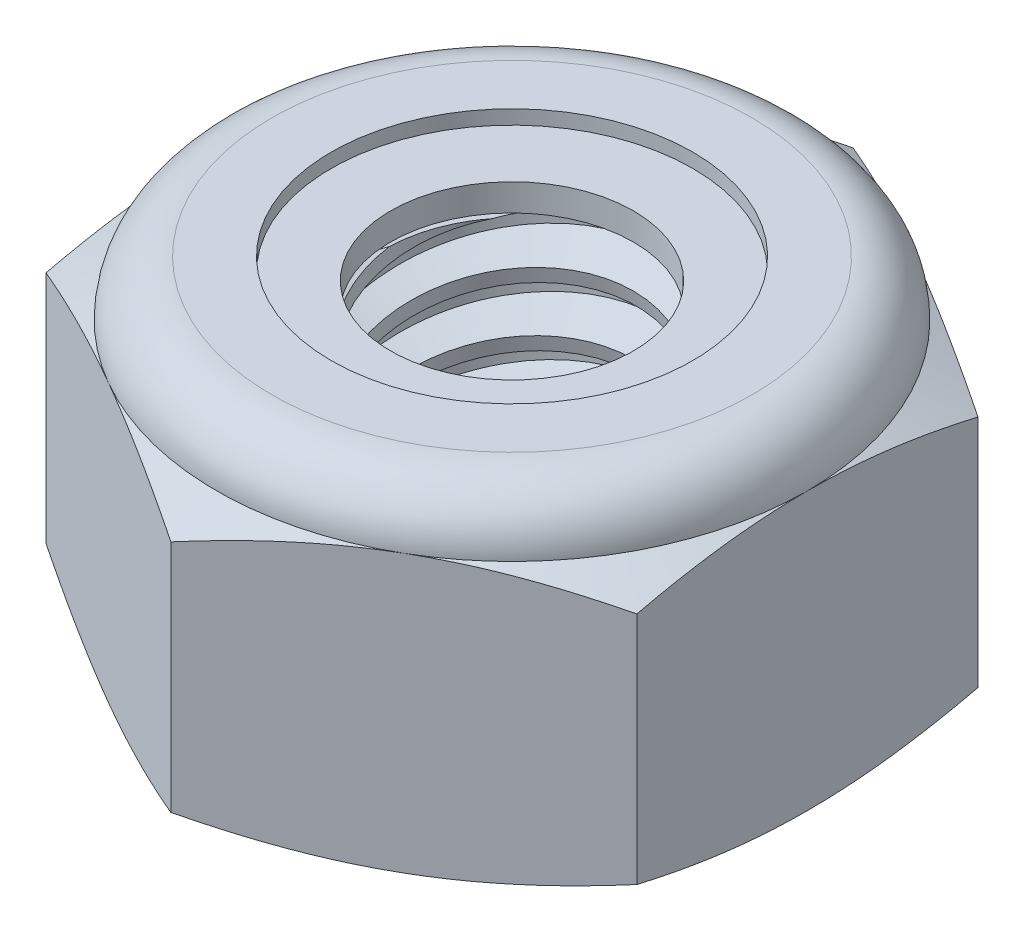
SolidWorks part; units mm, degrees
ref_plane "Front" through (0, 0, 0) normal (0, 0, 1) x (1, 0, 0)
ref_plane "Top" through (0, 0, 0) normal (0, 1, 0) x (1, 0, 0)
ref_plane "Right" through (0, 0, 0) normal (1, 0, 0) x (0, 0, -1)
sketch "Sketch1" plane through (0, 0, 0) normal (0, 1, 0) x (1, 0, 0)
  line L1 (0, 3.6662) -> (-3.175, 1.8331)
  line L2 (-3.175, 1.8331) -> (-3.175, -1.8331)
  line L3 (-3.175, -1.8331) -> (0, -3.6662)
  line L4 (0, -3.6662) -> (3.175, -1.8331)
  line L5 (3.175, -1.8331) -> (3.175, 1.8331)
  line L6 (3.175, 1.8331) -> (0, 3.6662)
  circle A0 centre (0, 0) radius 3.175 construction
  dimension "Hex Flats" = 6.35
extrude "Extrude1" add sketch "Sketch1" along normal blind 3.5719
sketch "Sketch2" plane through (0, 0, 0) normal (1, 0, 0) x (0, 0, -1)
  line L0 (-1.5875, 0) -> (-1.5875, 3.5719) construction
  line L1 (0, 0) -> (1.5875, 0)
  line L2 (0, 0) -> (0, 3.5719)
  line L3 (0, 3.5719) -> (1.5875, 3.5719)
  line L4 (1.5875, 0) -> (1.5875, 3.5719)
  line L5 (-1.8331, 3.5719) -> (1.8331, 3.5719) construction
  line L7 (0, -1.5875) -> (0, 0) construction
  dimension "Thread Dia" = 3.175
revolve "Revolve1" add sketch "Sketch2" angle 360 about L7
sketch "Sketch3" plane through (0, 0, 0) normal (1, 0, 0) x (0, 0, -1)
  line L0 (1.5875, 3.5719) -> (-1.5875, 3.5719) construction
  line L1 (-1.5875, 3.5719) -> (-1.5875, 2.9369) construction
  line L2 (-1.5875, 2.9369) -> (1.5875, 3.5719) construction
  line L3 (1.5875, 3.5719) -> (1.6031, 3.494) construction
  line L4 (1.6031, 3.494) -> (1.712, 2.9492)
  line L5 (1.712, 2.9492) -> (1.3361, 3.0764)
  line L6 (1.3361, 3.0764) -> (1.305, 3.2321)
  line L7 (1.305, 3.2321) -> (1.6031, 3.494)
  line L8 (1.3205, 3.1542) -> (1.6576, 3.2216) construction
  line L9 (1.5875, 3.5719) -> (1.5875, 3.2076) construction
  line L10 (1.5875, 3.2076) -> (-1.5875, 2.5726) construction
  line L11 (-1.5875, 2.5726) -> (-1.5875, 2.9369) construction
  line L12 (-0.1364, 3.5719) -> (0.1364, 2.2084) construction
  line L13 (-1.5875, 0) -> (-1.5875, 3.5719) construction
  line L14 (0, 3.5719) -> (1.5875, 3.5719) construction
  line L15 (1.5875, 0) -> (1.5875, 3.5719) construction
  point P13 (0, 2.8901)
  dimension "D1" = 0.0794
  dimension "D2" = 0.1588
  dimension "Thread Pitch" = 0.635
  dimension "D4" = 60
  dimension "D5" = 0.635
revolve "Cut-Revolve1" cut sketch "Sketch3" angle 360 about L12
pattern_linear "LPattern1" count 6 spacing 0.635 along (0, -1, 0) count 2 spacing 0.635 along (0, 1, 0) of "Cut-Revolve1"
sketch "Sketch4" plane through (0, 0, 0) normal (1, 0, 0) x (0, 0, -1)
  line L0 (0, 3.5719) -> (1.5875, 3.5719)
  line L1 (1.5875, 3.5719) -> (1.305, 3.4401)
  line L2 (1.305, 3.4401) -> (1.305, 0.1318)
  line L3 (1.305, 0.1318) -> (1.5875, 0)
  line L4 (1.5875, 0) -> (0, 0)
  line L5 (0, 0) -> (0, 3.5719)
  line L6 (1.5875, 0) -> (1.5875, 3.5719) construction
  line L7 (0, 3.5719) -> (1.5875, 3.5719) construction
  line L8 (0, 0) -> (1.5875, 0) construction
  line L9 (0, 0) -> (0, 3.5719) construction
  line L10 (0, 3.5719) -> (0, 3.8836) construction
  dimension "D1" = 25
revolve "Cut-Revolve2" cut sketch "Sketch4" angle 360 about L10
combine bodies "Combine1" operation type subtract main body 112 bodies to subtract 111
sketch "Sketch5" plane through (0, 0, 0) normal (1, 0, 0) x (0, 0, -1)
  line L0 (0, 0) -> (3.175, 0)
  line L1 (3.175, 0) -> (3.6662, 0.229)
  line L2 (3.6662, 0.229) -> (3.6662, 2.7475)
  line L3 (3.6662, 2.7475) -> (3.175, 2.9766)
  line L4 (2.5797, 3.5719) -> (2.5797, 4.8419)
  line L5 (2.5797, 4.8419) -> (4.9362, 4.8419)
  line L6 (4.9362, 4.8419) -> (4.9362, -1.27)
  line L7 (4.9362, -1.27) -> (0, -1.27)
  line L8 (0, -1.27) -> (0, 0)
  line L9 (3.175, 2.9766) -> (3.175, 0) construction
  line L10 (0, 0) -> (1.5875, 0) construction
  line L13 (3.6662, 1.4883) -> (4.9362, 1.4883) construction
  line L14 (3.6662, 3.5719) -> (3.6662, 0) construction
  line L15 (0, 0) -> (0, 4.8419) construction
  line L20 (0, 4.8419) -> (2.5797, 4.8419) construction
  line L22 (0, 3.5719) -> (1.5875, 3.5719) construction
  arc A0 (3.175, 2.9766) -> (2.5797, 3.5719) centre (2.5797, 2.9766) ccw
  dimension "D1" = 25
  dimension "D2" = 1.27
  dimension "D3" = 3.5719
  dimension "D4" = 0.5953
revolve "Cut-Revolve3" cut sketch "Sketch5" angle 360 about L15
sketch "Sketch6" plane through (0, 0, 0) normal (1, 0, 0) x (0, 0, -1)
  line L0 (0, 2.9766) -> (3.0226, 2.9766)
  line L1 (2.5797, 3.4195) -> (1.9423, 3.4195)
  line L2 (0, 4.8419) -> (0, 2.9766)
  line L3 (1.9423, 4.8419) -> (0, 4.8419)
  line L4 (0, 4.8419) -> (2.5797, 4.8419) construction
  line L5 (0, 0) -> (0, 4.8419) construction
  line L6 (0, 4.8419) -> (0, 44.323) construction
  line L7 (1.9423, 3.4195) -> (1.9423, 4.8419)
  line L8 (2.5797, 3.5719) -> (2.5797, 3.4195) construction
  line L9 (1.9423, 3.4195) -> (1.305, 3.4195) construction
  line L10 (1.305, 3.4195) -> (1.305, 3.4401) construction
  arc A0 (3.0226, 2.9766) -> (2.5797, 3.4195) centre (2.5797, 2.9766) ccw
  arc A1 (3.175, 2.9766) -> (2.5797, 3.5719) centre (2.5797, 2.9766) ccw construction
  dimension "D1" = 0.1524
revolve "Cut-Revolve4" cut sketch "Sketch6" angle 360 about L6
sketch "Sketch7" plane through (0, 0, 0) normal (1, 0, 0) x (0, 0, -1)
  line L0 (1.305, 3.0528) -> (2.9384, 3.0528)
  line L1 (2.5797, 3.3433) -> (1.305, 3.3433)
  line L2 (1.305, 3.3433) -> (1.305, 3.0528)
  line L3 (1.305, 3.0528) -> (0, 3.0528) construction
  line L4 (0, 3.0528) -> (0, 3.3433) construction
  line L5 (0, 3.3433) -> (1.305, 3.3433) construction
  line L6 (1.305, 3.0528) -> (1.305, 2.9766) construction
  line L7 (0, 2.9766) -> (3.0226, 2.9766) construction
  line L8 (2.5797, 3.3433) -> (2.5797, 3.4195) construction
  arc A0 (2.9384, 3.0528) -> (2.5797, 3.3433) centre (2.5797, 2.9766) ccw
  arc A2 (3.0226, 2.9766) -> (2.5797, 3.4195) centre (2.5797, 2.9766) ccw construction
  dimension "D1" = 0.0762
revolve "Revolve2" add sketch "Sketch7" angle 360 about L4
equation "\"D1@Sketch3\"=\"Thread Pitch@Sketch3\"/8"
equation "\"D2@Sketch3\"=\"Thread Pitch@Sketch3\"/4"
equation "\"D5@Sketch3\"=\"Thread Pitch@Sketch3\""
equation "\"D4@LPattern1\"=\"Thread Pitch@Sketch3\""
equation "\"D3@LPattern1\"=\"Thread Pitch@Sketch3\""
equation "\"D1@LPattern1\"=\"Height@Extrude1\"/\"Thread Pitch@Sketch3\""
equation "\"D4@Sketch5\"=\"Height@Extrude1\"/6"
